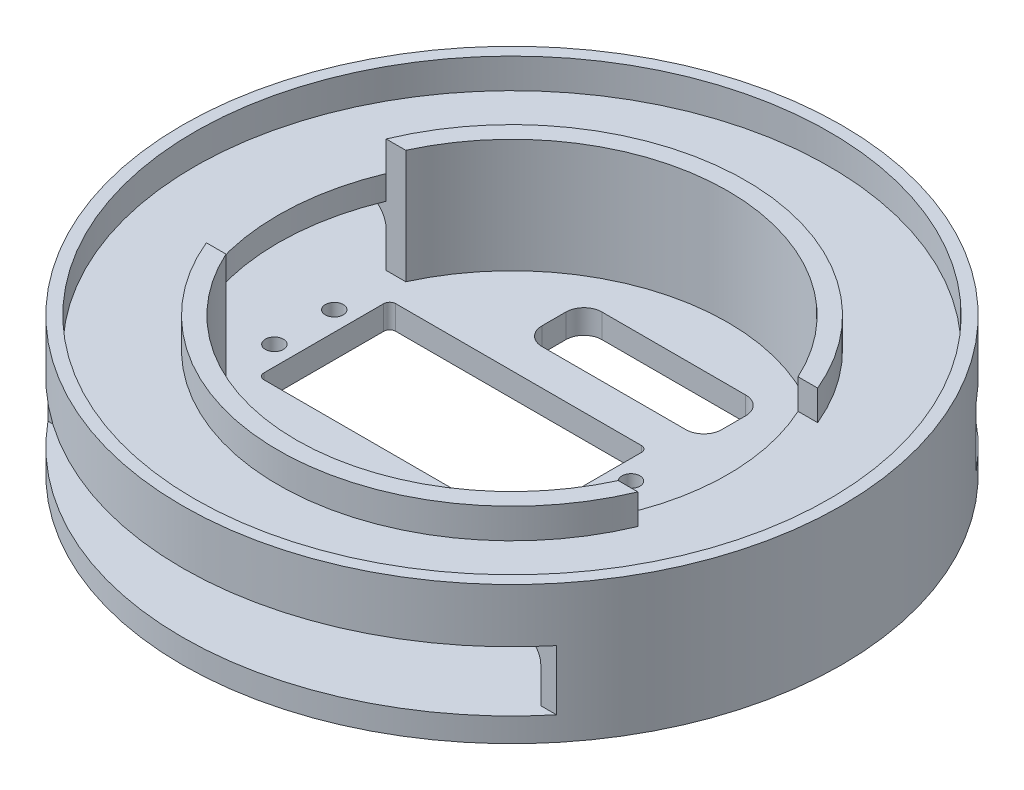
SolidWorks part; units mm, degrees
ref_plane "前视基准面" through (0, 0, 0) normal (0, 0, 1) x (1, 0, 0)
ref_plane "上视基准面" through (0, 0, 0) normal (0, 1, 0) x (1, 0, 0)
ref_plane "右视基准面" through (0, 0, 0) normal (1, 0, 0) x (0, 0, -1)
other "Configuration Table"
sketch "草图1" plane through (0, 0, 0) normal (0, 1, 0) x (1, 0, 0)
  circle A0 centre (0, 0) radius 55
  dimension "D1" = 110
extrude "凸台-拉伸1" add sketch "草图1" along normal blind 4
sketch "草图2" plane through (0, 4, 0) normal (0, 1, 0) x (1, 0, 0)
  line L0 (0, 0) -> (79.599, 0) construction
  line L1 (0, -35) -> (79.599, -35) construction
  line L2 (0, 35) -> (79.599, 35) construction
  line L3 (0, 0) -> (0, 58.6993) construction
  line L4 (0, -35) -> (-79.599, -35) construction
  line L5 (0, 35) -> (-79.599, 35) construction
  line L6 (-42.4264, 35) -> (-39.7995, 35)
  line L7 (-42.4264, -35) -> (-39.7995, -35)
  line L8 (42.4264, -35) -> (39.7995, -35)
  line L9 (42.4264, 35) -> (39.7995, 35)
  circle A0 centre (0, 0) radius 55
  circle A1 centre (0, 0) radius 53
  circle M2 centre (0, 0) radius 55
  dimension "D1" = 110
  dimension "D2" = 106
  dimension "D3" = 35
  dimension "D4" = 35
extrude "凸台-拉伸2" add sketch "草图2" along normal blind 10 contours A1 L6 L7 M2 | A1 L8 L9 M2 region at (-41.113, 4, -34.2837) region at (51.0871, 4, -18.3528)
sketch "草图3" plane through (0, 0, 0) normal (0, -1, 0) x (1, 0, 0)
  line L0 (0, 0) -> (0, 59.6138) construction
  line L1 (0, 0) -> (72.5882, 0) construction
  line L3 (-31.4, -11) -> (11.6, -11)
  line L4 (-31.4, -11) -> (-31.4, 11)
  line L5 (-31.4, 11) -> (11.6, 11)
  line L6 (11.6, -11) -> (11.6, 11)
  line L7 (-31.4, -11) -> (11.6, 11) construction
  line L8 (-31.4, 11) -> (11.6, -11) construction
  circle A0 centre (14.85, 5) radius 1.5
  circle A1 centre (14.85, -5) radius 1.5
  circle A2 centre (-34.65, 5) radius 1.5
  circle A3 centre (-34.65, -5) radius 1.5
  point P12 (-9.9, 0)
  dimension "D1" = 3
  dimension "D2" = 10
  dimension "D4" = 3
  dimension "D5" = 10
  dimension "D6" = 49.5
  dimension "D3" = 14.85
  dimension "D7" = 24.75
  dimension "D8" = 22
  dimension "D9" = 43
  dimension "D10" = 0
extrude "切除-拉伸1" cut sketch "草图3" against normal blind 6
fillet "圆角1" radius 1 4 edges at (-31.4, 2, 11) (-31.4, 2, -11) (11.6, 2, 11) (11.6, 2, -11)
sketch "草图4" plane through (0, 4, 0) normal (0, 1, 0) x (1, 0, 0)
  line L0 (0, 0) -> (74.6459, 0) construction
  line L1 (0, -15) -> (74.6459, -15) construction
  line L2 (0, 15) -> (74.6459, 15) construction
  line L3 (0, 0) -> (0, 75.899) construction
  line L4 (0, -15) -> (-74.6459, -15) construction
  line L5 (0, 15) -> (-74.6459, 15) construction
  line L6 (32.7261, 15) -> (36, 15)
  line L7 (32.7261, -15) -> (36, -15)
  line L8 (-36, 15) -> (-32.7261, 15)
  line L9 (-36, -15) -> (-32.7261, -15)
  circle A0 centre (0, 0) radius 39
  circle A1 centre (0, 0) radius 36
  dimension "D1" = 78
  dimension "D2" = 72
  dimension "D3" = 15
  dimension "D4" = 15
extrude "凸台-拉伸3" add sketch "草图4" along normal blind 10 contours A1 L6 A0 L8 | A1 L9 A0 L7 region at (0, 4, -36.7589) region at (34.3631, 4, 15.7589)
sketch "草图5" plane through (0, 14, 0) normal (0, 1, 0) x (1, 0, 0)
  circle A1 centre (0, 0) radius 55
  circle A2 centre (0, 0) radius 36
  dimension "D1" = 72
  dimension "D2" = 110
extrude "凸台-拉伸4" add sketch "草图5" along normal blind 4
sketch "草图6" plane through (0, 18, 0) normal (0, 1, 0) x (1, 0, 0)
  line L0 (32.7261, -15) -> (36, -15) construction
  line L1 (32.7261, 15) -> (36, 15) construction
  line L2 (-36, -15) -> (-32.7261, -15) construction
  line L3 (-36, 15) -> (-32.7261, 15) construction
  line L4 (32.7261, -15) -> (36, -15)
  line L5 (32.7261, 15) -> (36, 15)
  line L6 (-36, -15) -> (-32.7261, -15)
  line L7 (-36, 15) -> (-32.7261, 15)
  circle A0 centre (0, 0) radius 36 construction
  circle A1 centre (0, 0) radius 39 construction
  circle A2 centre (0, 0) radius 36
  circle A3 centre (0, 0) radius 39
  circle A4 centre (0, 0) radius 55
  circle A5 centre (0, 0) radius 53
  circle M1 centre (0, 0) radius 55
  circle M2 centre (0, 0) radius 36
  dimension "D1" = 110
  dimension "D2" = 106
extrude "凸台-拉伸5" add sketch "草图6" along normal blind 5 contours A5 M1 | L5 A3 L7 M2 | L6 A3 L4 M2 region at (34.3631, 18, 15.7589) region at (-34.3631, 18, -15.7589) region at (-53.4444, 18, 0)
sketch "草图7" plane through (0, 18, 0) normal (0, 1, 0) x (1, 0, 0)
  line L0 (-32.7261, 15) -> (-36, 15)
  line L1 (-32.7261, -15) -> (-36, -15)
  line L2 (0, 15) -> (-74.6459, 15) construction
  arc A0 (-32.7261, -15) -> (-32.7261, 15) centre (0, 0) cw
  arc A1 (-36, -15) -> (-36, 15) centre (0, 0) cw
  line M1 (-36, -15) -> (-32.7261, -15)
  arc M2 (-32.7261, -15) -> (-32.7261, 15) centre (0, 0) cw
  line M3 (-32.7261, 15) -> (-36, 15)
extrude "切除-拉伸2" cut sketch "草图7" against normal blind 4 contours A1 M1 M2 M3 region at (-36.4485, 18, 0)
fillet "圆角2" radius 4 4 edges at (0, 14, -39) (53, 14, 0) (-53, 14, 0) (0, 14, 39)
sketch "草图8" plane through (0, 4, 0) normal (0, 1, 0) x (1, 0, 0)
  line L0 (0, 0) -> (77.6936, 0) construction
  line L1 (0, 0) -> (0, 70.4208) construction
  line L2 (-15, -27) -> (15, -27)
  line L3 (-15, 17) -> (15, 17)
  line L4 (-15, 17) -> (-15, 27)
  line L5 (-15, 27) -> (15, 27)
  line L6 (15, 17) -> (15, 27)
  line L7 (-15, 17) -> (15, 27) construction
  line L8 (-15, 27) -> (15, 17) construction
  line L9 (15, -17) -> (15, -27)
  line L10 (-15, -17) -> (15, -17)
  line L11 (-15, -17) -> (-15, -27)
  line L12 (-15, -27) -> (15, -17) construction
  line L13 (-15, -17) -> (15, -27) construction
  point P3 (0, 22)
  point P13 (0, -22)
  dimension "D1" = 30
  dimension "D2" = 10
  dimension "D3" = 22
extrude "切除-拉伸3" cut sketch "草图8" against normal blind 10
fillet "圆角3" radius 3 8 edges at (-15, 2, -17) (15, 2, -17) (15, 2, -27) (-15, 2, -27) (-15, 2, 17) (15, 2, 17) (-15, 2, 27) (15, 2, 27)
